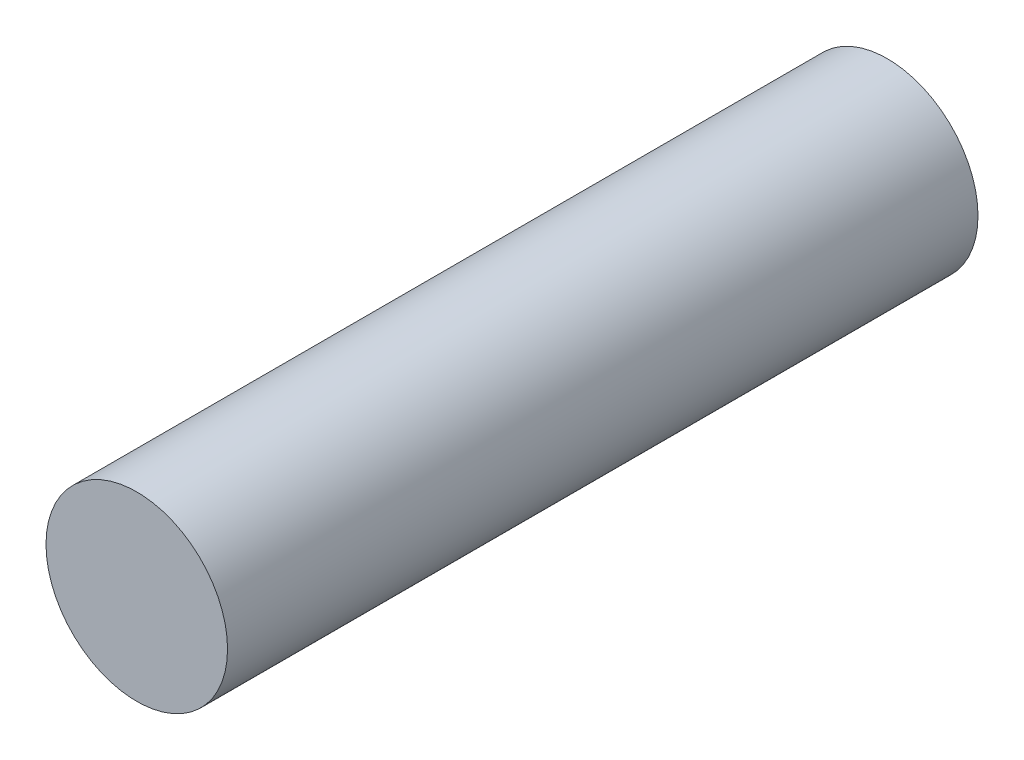
SolidWorks part; units mm, degrees
ref_plane "Front Plane" through (0, 0, 0) normal (0, 0, 1) x (1, 0, 0)
ref_plane "Top Plane" through (0, 0, 0) normal (0, 1, 0) x (1, 0, 0)
ref_plane "Right Plane" through (0, 0, 0) normal (1, 0, 0) x (0, 0, -1)
sketch "Sketch2" plane through (0, 0, 0) normal (0, 0, 1) x (1, 0, 0)
  line L0 (0, 0) -> (-80, 0) construction
  circle A0 centre (-80, 0) radius 12.7
  dimension "D2" = 25.4
  dimension "D1" = 80
extrude "Boss-Extrude1" add sketch "Sketch2" along normal mid plane 105
